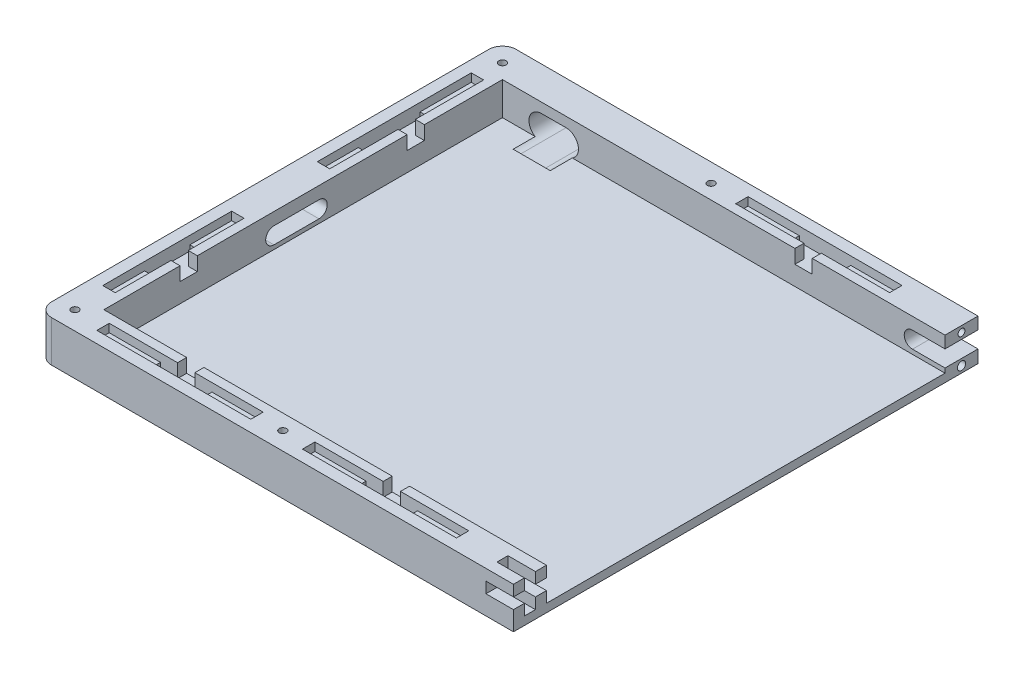
SolidWorks part; units mm, degrees
ref_plane "Front Plane" through (0, 0, 0) normal (0, 0, 1) x (1, 0, 0)
ref_plane "Top Plane" through (0, 0, 0) normal (0, 1, 0) x (1, 0, 0)
ref_plane "Right Plane" through (0, 0, 0) normal (1, 0, 0) x (0, 0, -1)
sketch "Sketch1" plane through (0, 0, 0) normal (0, 1, 0) x (1, 0, 0)
  line L0 (-185.215, 0) -> (43.0487, 0) construction
  line L1 (0, 72.5) -> (-161, 72.5)
  line L2 (0, 215.1028) -> (0, -153.2812) construction
  line L3 (-161, 72.5) -> (-161, -72.5)
  line L4 (-161, -72.5) -> (0, -72.5)
  line L5 (0, 72.5) -> (0, -72.5)
  point P9 (0, 0)
  dimension "D1" = 161
  dimension "D2" = 72.5
extrude "Boss-Extrude1" add sketch "Sketch1" along normal blind 3
sketch "Sketch2" plane through (0, 0, 0) normal (0, 1, 0) x (1, 0, 0)
  line L0 (-224.2217, 0) -> (91.1792, 0) construction
  line L1 (0, 149.3369) -> (0, -151.0656) construction
  line L2 (0, 72.5) -> (0, 84.5)
  line L3 (0, 84.5) -> (-173, 84.5)
  line L4 (-173, 84.5) -> (-173, -84.5)
  line L5 (-173, -84.5) -> (0, -84.5)
  line L6 (0, -84.5) -> (0, -72.5)
  line L8 (-161, 72.5) -> (-161, -72.5) construction
  line L13 (0, -72.5) -> (0, 72.5)
  line L14 (0, 72.5) -> (-161, 72.5)
  line L15 (-161, 72.5) -> (-161, -72.5)
  line L16 (-161, -72.5) -> (0, -72.5)
  line L18 (0, 72.5) -> (-161, 72.5)
  line L19 (-161, 72.5) -> (-161, -72.5)
  line L20 (-161, -72.5) -> (0, -72.5)
  dimension "D1" = 12
  dimension "D2" = 12
  dimension "D3" = 12
  dimension "D4" = 0
extrude "Boss-Extrude2" add sketch "Sketch2" along normal blind 15
sketch "Sketch3" plane through (0, 15, 0) normal (0, 1, 0) x (1, 0, 0)
  line L0 (-161, 72.5) -> (-161, 44.1) construction
  line L1 (-161, -72.5) -> (-161, 72.5) construction
  line L2 (-161, -72.5) -> (-161, -44.8) construction
  line L3 (-161, 44.1) -> (-161, 37.8)
  line L4 (-161, 44.1) -> (-164.3, 44.1)
  line L5 (-161, 37.8) -> (-164.3, 37.8)
  line L6 (-164.3, 44.1) -> (-164.3, 68.95)
  line L7 (-164.3, 37.8) -> (-164.3, 12.95)
  line L8 (-164.3, 68.95) -> (-168.8, 68.95)
  line L9 (-168.8, 68.95) -> (-168.8, 12.95)
  line L10 (-168.8, 12.95) -> (-164.3, 12.95)
  line L11 (-161, 72.5) -> (-161, -72.5) construction
  line L12 (-24.95, -75.8) -> (-49.8, -75.8)
  line L13 (-161, -38.5) -> (-161, -44.8)
  line L14 (-161, -38.5) -> (-164.3, -38.5)
  line L15 (-161, -44.8) -> (-164.3, -44.8)
  line L16 (-164.3, -38.5) -> (-164.3, -18.2)
  line L17 (-164.3, -18.2) -> (-168.8, -18.2)
  line L18 (-168.8, -18.2) -> (-168.8, -65.1)
  line L19 (-168.8, -65.1) -> (-164.3, -65.1)
  line L20 (-164.3, -65.1) -> (-164.3, -44.8)
  line L21 (-24.95, -80.3) -> (-24.95, -75.8)
  line L22 (-80.95, -80.3) -> (-24.95, -80.3)
  line L23 (-80.95, -75.8) -> (-80.95, -80.3)
  line L24 (-56.1, -75.8) -> (-80.95, -75.8)
  line L25 (-56.1, -72.5) -> (-56.1, -75.8)
  line L26 (-49.8, -72.5) -> (-56.1, -72.5)
  line L27 (-49.8, -75.8) -> (-49.8, -72.5)
  line L28 (-99.75, -80.3) -> (-99.75, -75.8)
  line L29 (-155.75, -80.3) -> (-99.75, -80.3)
  line L30 (-155.75, -75.8) -> (-155.75, -80.3)
  line L31 (-130.9, -75.8) -> (-155.75, -75.8)
  line L32 (-130.9, -72.5) -> (-130.9, -75.8)
  line L33 (-124.6, -72.5) -> (-130.9, -72.5)
  line L34 (-124.6, -75.8) -> (-124.6, -72.5)
  line L35 (-99.75, -75.8) -> (-124.6, -75.8)
  line L36 (0, -72.5) -> (-161, -72.5) construction
  line L37 (-161, -72.5) -> (0, -72.5) construction
  line L38 (-48.3, 75.8) -> (-48.3, 72.5)
  line L39 (-23.45, 75.8) -> (-48.3, 75.8)
  line L40 (-23.45, 80.3) -> (-23.45, 75.8)
  line L41 (-79.45, 80.3) -> (-23.45, 80.3)
  line L42 (-79.45, 75.8) -> (-79.45, 80.3)
  line L43 (-54.6, 75.8) -> (-79.45, 75.8)
  line L44 (-54.6, 72.5) -> (-54.6, 75.8)
  line L45 (-48.3, 72.5) -> (-54.6, 72.5)
  line L46 (-161, 72.5) -> (0, 72.5) construction
  dimension "D1" = 28.4
  dimension "D2" = 56
  dimension "D3" = 6.3
  dimension "D4" = 3.3
  dimension "D5" = 6.3
  dimension "D6" = 20.3
  dimension "D7" = 4.5
  dimension "D8" = 4.5
  dimension "D9" = 27.7
  dimension "D10" = 3.3
  dimension "D11" = 30.1
  dimension "D12" = 6.3
  dimension "D13" = 3.3
  dimension "D14" = 4.5
  dimension "D15" = 56
  dimension "D16" = 68.5
  dimension "D17" = 6.3
  dimension "D18" = 3.3
  dimension "D19" = 4.5
  dimension "D20" = 56
  dimension "D21" = 6.3
  dimension "D22" = 3.3
  dimension "D23" = 4.5
  dimension "D24" = 56
  dimension "D25" = 48.3
extrude "Cut-Extrude1" cut sketch "Sketch3" against normal blind 3
sketch "Sketch4" plane through (0, 12, 0) normal (0, 1, 0) x (1, 0, 0)
  line L1 (-54.6, 72.5) -> (-48.3, 72.5)
  line L2 (-48.3, 72.5) -> (-48.3, 75.8)
  line L3 (-48.3, 75.8) -> (-35.875, 75.8) construction
  line L4 (-130.9, -75.8) -> (-143.325, -75.8) construction
  line L5 (-54.6, 75.8) -> (-67.025, 75.8) construction
  line L6 (-79.45, 75.8) -> (-54.6, 75.8) construction
  line L7 (-48.3, 75.8) -> (-23.45, 75.8) construction
  line L10 (-54.6, 72.5) -> (-54.6, 75.8)
  line L14 (-48.3, 75.8) -> (-42.0875, 75.8)
  line L15 (-161, 44.1) -> (-161, 37.8)
  line L16 (-161, 37.8) -> (-164.3, 37.8)
  line L17 (-164.3, 44.1) -> (-164.3, 56.525) construction
  line L18 (-164.3, 44.1) -> (-164.3, 68.95) construction
  line L19 (-164.3, 37.8) -> (-164.3, 25.375) construction
  line L20 (-164.3, 12.95) -> (-164.3, 37.8) construction
  line L21 (-161, 44.1) -> (-164.3, 44.1)
  line L24 (-130.9, -75.8) -> (-155.75, -75.8) construction
  line L26 (-124.6, -75.8) -> (-112.175, -75.8) construction
  line L30 (-164.3, 44.1) -> (-164.3, 50.3125)
  line L31 (-164.3, 50.3125) -> (-168.8, 50.3125)
  line L32 (-168.8, 68.95) -> (-168.8, 12.95) construction
  line L33 (-168.8, 50.3125) -> (-168.8, 27.8502)
  line L34 (-168.8, 68.95) -> (-168.8, 12.95) construction
  line L35 (-168.8, 27.8502) -> (-164.3, 27.8502)
  line L36 (-164.3, 27.8502) -> (-164.3, 37.8)
  line L37 (-164.3, -38.5) -> (-164.3, -28.35) construction
  line L38 (-164.3, -38.5) -> (-164.3, -18.2) construction
  line L39 (-168.8, -33.425) -> (-168.8, -49.875)
  line L40 (-164.3, -65.1) -> (-164.3, -44.8) construction
  line L41 (-164.3, -33.425) -> (-168.8, -33.425)
  line L42 (-168.8, -18.2) -> (-168.8, -65.1) construction
  line L43 (-164.3, -44.8) -> (-164.3, -54.95) construction
  line L44 (-168.8, -49.875) -> (-164.3, -49.875)
  line L45 (-164.3, -49.875) -> (-164.3, -44.8)
  line L46 (-164.3, -44.8) -> (-161, -44.8)
  line L47 (-161, -44.8) -> (-161, -38.5)
  line L48 (-161, -38.5) -> (-164.3, -38.5)
  line L49 (-164.3, -38.5) -> (-164.3, -33.425)
  line L50 (-99.75, -75.8) -> (-124.6, -75.8) construction
  line L51 (-130.9, -72.5) -> (-130.9, -75.8)
  line L52 (-130.9, -75.8) -> (-137.1125, -75.8)
  line L53 (-137.1125, -75.8) -> (-137.1125, -80.3)
  line L54 (-155.75, -80.3) -> (-99.75, -80.3) construction
  line L55 (-137.1125, -80.3) -> (-118.3875, -80.3)
  line L56 (-118.3875, -80.3) -> (-118.3875, -75.8)
  line L59 (-124.6, -72.5) -> (-130.9, -72.5)
  line L60 (-124.6, -72.5) -> (-124.6, -75.8)
  line L61 (-124.6, -75.8) -> (-118.3875, -75.8)
  line L62 (-56.1, -75.8) -> (-68.525, -75.8) construction
  line L63 (-56.1, -75.8) -> (-80.95, -75.8) construction
  line L64 (-49.8, -75.8) -> (-37.375, -75.8) construction
  line L65 (-24.95, -75.8) -> (-49.8, -75.8) construction
  line L66 (-56.1, -75.8) -> (-62.3125, -75.8)
  line L67 (-62.3125, -75.8) -> (-62.3125, -80.3)
  line L68 (-80.95, -80.3) -> (-24.95, -80.3) construction
  line L69 (-62.3125, -80.3) -> (-43.5875, -80.3)
  line L70 (-43.5875, -80.3) -> (-43.5875, -75.8)
  line L71 (-43.5875, -75.8) -> (-49.8, -75.8)
  line L72 (-49.8, -75.8) -> (-49.8, -72.5)
  line L73 (-49.8, -72.5) -> (-56.1, -72.5)
  line L74 (-56.1, -72.5) -> (-56.1, -75.8)
  line L80 (-54.6, 75.8) -> (-60.8125, 75.8)
  line L81 (-60.8125, 75.8) -> (-60.8125, 80.3)
  line L82 (-23.45, 80.3) -> (-79.45, 80.3) construction
  line L83 (-60.8125, 80.3) -> (-42.0875, 80.3)
  line L84 (-23.45, 80.3) -> (-79.45, 80.3) construction
  line L85 (-42.0875, 80.3) -> (-42.0875, 75.8)
extrude "Cut-Extrude2" cut sketch "Sketch4" against normal blind 2
sketch "Sketch5" plane through (-173, 0, 0) normal (-1, 0, 0) x (0, 0, 1)
  line L0 (0, 7.5) -> (32.6582, 7.5) construction
  line L1 (-84.5, 7.5) -> (0, 7.5) construction
  line L2 (-84.5, 15) -> (-84.5, 0) construction
  line L3 (-84.5, 11.8257) -> (-8.75, 11.8257) construction
  line L4 (-5.75, 10.5) -> (10.63, 10.5)
  line L5 (-5.75, 4.5) -> (10.63, 4.5)
  line L8 (-8.75, 4.845) -> (-8.75, 10.155) construction
  arc A0 (-5.75, 4.5) -> (-5.75, 10.5) centre (-5.75, 7.5) cw
  arc A1 (10.63, 10.5) -> (10.63, 4.5) centre (10.63, 7.5) cw
  point P17 (-5.75, 10.5)
  point P21 (-8.75, 7.5)
  dimension "D2" = 3
  dimension "D1" = 16.38
  dimension "D3" = 75.75
extrude "Cut-Extrude3" cut sketch "Sketch5" against normal blind 12
sketch "Sketch7" plane through (0, 0, -84.5) normal (0, 0, -1) x (-1, 0, 0)
  line L0 (60.062, 7.6343) -> (-60.062, 7.6343) construction
  line L1 (0, 0) -> (173, 0) construction
  line L2 (14.8425, 7.6343) -> (14.8425, 12.6467) construction
  line L3 (-4.5375, 10.6343) -> (11.8425, 10.6343)
  line L4 (-4.5375, 4.6343) -> (11.8425, 4.6343)
  line L5 (0, 11.4722) -> (14.8425, 11.4722) construction
  line L6 (0, 15) -> (0, 0) construction
  arc A0 (-4.5375, 4.6343) -> (-4.5375, 10.6343) centre (-4.5375, 7.6343) cw
  arc A1 (11.8425, 10.6343) -> (11.8425, 4.6343) centre (11.8425, 7.6343) cw
  point P3 (0, 7.6343)
  dimension "D3" = 3
  dimension "D1" = 14.8425
  dimension "D2" = 16.38
  dimension "D4" = 7.6343
extrude "Cut-Extrude5" cut sketch "Sketch7" against normal blind 12
sketch "Sketch8" plane through (0, 0, -84.5) normal (0, 0, -1) x (-1, 0, 0)
  line L0 (173, 7.5) -> (143.1877, 7.5) construction
  line L1 (173, 15) -> (173, 0) construction
  line L2 (173, 7.9) -> (146.86, 7.9) construction
  line L3 (146.86, 7.9) -> (137.86, 7.9) construction
  line L4 (0, 15) -> (173, 15) construction
  line L5 (137.86, 11.4) -> (146.86, 11.4)
  line L6 (137.86, 2.4) -> (146.86, 2.4)
  line L7 (164.2575, 6.9) -> (140.1095, 6.9) construction
  line L8 (142.36, 7.9) -> (142.36, 5.9) construction
  line L9 (146.86, 7.9) -> (146.86, 15.4665) construction
  arc A0 (137.86, 2.4) -> (137.86, 11.4) centre (137.86, 6.9) cw
  arc A1 (146.86, 11.4) -> (146.86, 2.4) centre (146.86, 6.9) cw
  point P19 (142.36, 6.9)
  dimension "D5" = 9
  dimension "D1" = 26.14
  dimension "D2" = 9
  dimension "D3" = 7.1
  dimension "D4" = 9
  dimension "D6" = 1
  dimension "2" = 2
extrude "Cut-Extrude6" cut sketch "Sketch8" against normal blind 20
sketch "Sketch10" plane through (0, 0, 0) normal (1, 0, 0) x (0, 0, -1)
  line L0 (-72.5, 3) -> (-72.5, 15) construction
  line L1 (-72.5, 15) -> (-84.5, 15) construction
  line L2 (-84.5, 15) -> (-84.5, 3) construction
  line L3 (-84.5, 15) -> (-84.5, 0) construction
  line L4 (-84.5, 3) -> (-72.5, 3) construction
  line L5 (-72.5, 3) -> (-84.5, 15) construction
  line L6 (-84.5, 15) -> (-72.5, 15) construction
  line L7 (-72.5, 15) -> (-84.5, 3) construction
  line L8 (-78.5, 15.3824) -> (-78.5, 3) construction
  line L9 (-84.5, 9) -> (-71.292, 9) construction
  line L10 (-80.5, 15) -> (-76.5, 15)
  line L11 (-72.5, 7) -> (-72.5, 11)
  line L12 (-76.5, 3) -> (-80.5, 3)
  line L13 (-84.5, 7) -> (-84.5, 11)
  line L14 (-80.5, 15) -> (-80.5, 11)
  line L15 (-80.5, 11) -> (-84.5, 11)
  line L16 (-84.5, 7) -> (-80.5, 7)
  line L17 (-80.5, 7) -> (-80.5, 3)
  line L18 (-76.5, 3) -> (-76.5, 7)
  line L19 (-76.5, 7) -> (-72.5, 7)
  line L20 (-72.5, 11) -> (-76.5, 11)
  line L21 (-76.5, 11) -> (-76.5, 15)
  line L22 (-78.5, 9) -> (-78.5, 15) construction
  line L23 (-72.5, 9) -> (-84.5, 9) construction
  point P15 (-78.5, 15)
  point P19 (-72.5, 9)
  point P22 (-78.5, 3)
  point P25 (-84.5, 9)
  dimension "D1" = 4
  dimension "D2" = 4
  dimension "D3" = 4
  dimension "D4" = 4
  dimension "D5" = 0
extrude "Cut-Extrude8" cut sketch "Sketch10" against normal blind 10
fillet "Fillet2" radius 5 1 edges at (-173, 7.5, 84.5)
fillet "Fillet3" radius 5 1 edges at (-173, 7.5, -84.5)
sketch "Sketch11" plane through (0, 0, 0) normal (1, 0, 0) x (0, 0, -1)
  line L0 (72.5, 4.6343) -> (84.5, 4.6343) construction
  line L1 (72.5, 4.6343) -> (72.5, 0) construction
  line L2 (-84.5, 0) -> (84.5, 0) construction
  line L3 (72.5, 0) -> (84.5, 0) construction
  line L4 (84.5, 0) -> (84.5, 4.6343) construction
  line L5 (78.5, 4.6343) -> (78.5, 0) construction
  line L6 (72.5, 2.3172) -> (84.5, 2.3172) construction
  line L7 (72.5, 15) -> (72.5, 10.6343) construction
  line L8 (72.5, 10.6343) -> (84.5, 10.6343) construction
  line L9 (84.5, 10.6343) -> (84.5, 15) construction
  line L10 (84.5, 15) -> (72.5, 15) construction
  line L11 (72.5, 15) -> (78.5, 15) construction
  line L12 (78.5, 15) -> (78.5, 10.6343) construction
  line L13 (78.5, 10.6343) -> (72.5, 10.6343) construction
  line L14 (72.5, 10.6343) -> (72.5, 12.8172) construction
  line L15 (72.5, 12.8172) -> (84.5, 12.8172) construction
  circle A0 centre (78.5, 2.3172) radius 1.5
  circle A1 centre (78.5, 12.8172) radius 1.25
  dimension "D1" = 3
  dimension "D2" = 2.5
extrude "Cut-Extrude9" cut sketch "Sketch11" against normal blind 10
sketch "Sketch12" plane through (0, 0, 0) normal (0, -1, 0) x (-1, 0, 0)
  circle A0 centre (166.2678, -77.7678) radius 1.325
  circle A1 centre (90.35, -78.05) radius 1.325
  circle A2 centre (-80.0525, -78.05) radius 1.325
  circle A3 centre (-164.8078, -77.7678) radius 1.325
  circle A4 centre (-164.8078, 77.7678) radius 1.325
  circle A5 centre (-80.0525, 78.05) radius 1.325
  circle A6 centre (90.35, 77.7678) radius 1.325
  circle A7 centre (166.2678, 77.7678) radius 1.325
  circle A9 centre (90.35, -78.05) radius 3
  circle A10 centre (-80.0525, -78.05) radius 3
  circle A11 centre (-164.8078, -77.7678) radius 3
  circle A12 centre (-164.8078, 77.7678) radius 3
  circle A13 centre (-80.0525, 78.05) radius 3
  circle A14 centre (90.35, 77.7678) radius 3
  circle A15 centre (166.2678, 77.7678) radius 3
  circle A16 centre (166.2678, -77.7678) radius 3
  dimension "D1" = 2.65
  dimension "D2" = 2.65
  dimension "D3" = 2.65
  dimension "D4" = 2.65
  dimension "D5" = 2.65
  dimension "D6" = 2.65
  dimension "D7" = 2.65
  dimension "D8" = 2.65
  dimension "D9" = 6
  dimension "D10" = 6
  dimension "D11" = 6
  dimension "D12" = 6
  dimension "D13" = 6
  dimension "D14" = 6
  dimension "D15" = 6
  dimension "D16" = 6
extrude "Cut-Extrude10" cut sketch "Sketch12" against normal blind 17 contours A0 | A1 | A2 | A3 | A4 | A5 | A6 | A7
sketch "Sketch13" plane through (0, 0, 0) normal (0, -1, 0) x (1, 0, 0)
  circle A0 centre (-166.2678, -77.7678) radius 3
  circle A1 centre (-90.35, -77.7678) radius 3
  circle A2 centre (-166.2678, 77.7678) radius 3
  circle A3 centre (-90.35, 78.05) radius 3
  dimension "D1" = 6
  dimension "D2" = 6
  dimension "D3" = 6
  dimension "D4" = 6
extrude "Cut-Extrude11" cut sketch "Sketch13" against normal blind 5
sketch "Sketch14" plane through (0, 0, 0) normal (0, -1, 0) x (-1, 0, 0)
  line L0 (168, -84.5) -> (0, -84.5) construction
  line L1 (173, 79.5) -> (173, -79.5) construction
  line L2 (0, 84.5) -> (168, 84.5) construction
  circle A0 centre (153, -64.5) radius 6.25
  circle A1 centre (153, 64.5) radius 6.25
  point P0 (153, -64.5)
  dimension "D3" = 12.5
  dimension "D4" = 12.5
  dimension "D1" = 20
  dimension "D2" = 20
  dimension "D5" = 20
  dimension "D6" = 20
extrude "Cut-Extrude12" cut sketch "Sketch14" against normal blind 1
